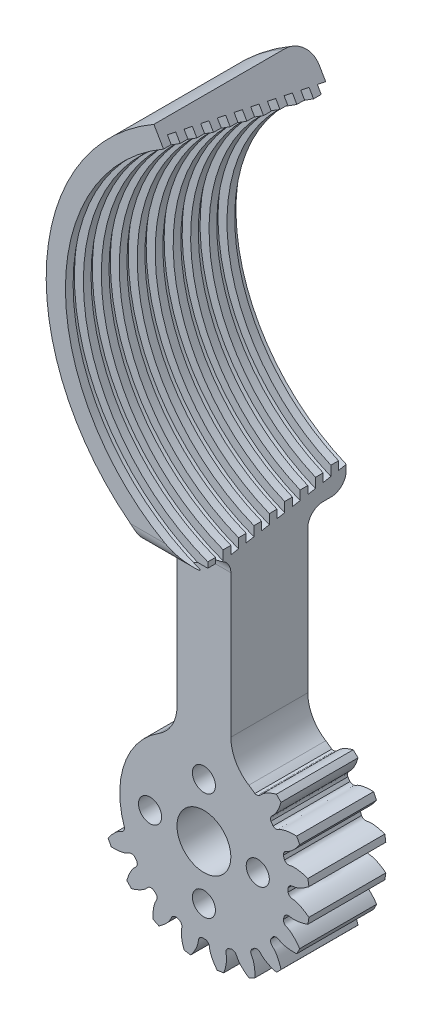
SolidWorks part; units mm, degrees
note: '?' marks a value the reader was unsure of.
material "聚脂树脂"
ref_plane "前视基准面" through (0, 0, 0) normal (0, 0, 1) x (1, 0, 0)
ref_plane "上视基准面" through (0, 0, 0) normal (0, 1, 0) x (1, 0, 0)
ref_plane "右视基准面" through (0, 0, 0) normal (1, 0, 0) x (0, 0, -1)
other "Configuration Table"
sketch "草图1" plane through (0, 0, 0) normal (0, 0, 1) x (1, 0, 0)
  circle A0 centre (0, 0) radius 13.75
extrude "凸台-拉伸1" add sketch "草图1" along normal blind 10
ref_axis "基准轴1" through (0, 0, -1.5) along (0, 0, 1)?
sketch "草图2" plane through (0, 0, 0) normal (0, 0, 1) x (1, 0, 0)
  line L0 (0, 0) -> (0, 13.75) construction
  circle A0 centre (0, 0) radius 13.75 construction
  arc A1 (0.2416, 10.9348) -> (-0.2416, 10.9348) centre (0, 0) ccw
  arc A2 (3.9764, 15.6228) -> (-3.9764, 15.6228) centre (0, 0) ccw
  spline S0 degree 3 poles (0.2416, 10.9348) (0.764, 11.1168) (0.6964, 11.4839) (0.7661, 11.8375) (0.7736, 11.8719) (0.7829, 11.9108) (0.7941, 11.954) (0.8075, 12.0015) (0.8231, 12.0532) (0.8413, 12.1091) (0.8621, 12.169) (0.8857, 12.2329) (0.9123, 12.3007) (0.9421, 12.3723) (0.9752, 12.4476) (1.0117, 12.5264) (1.0519, 12.6088) (1.0959, 12.6945) (1.1438, 12.7834) (1.1957, 12.8755) (1.2519, 12.9705) (1.3125, 13.0684) (1.3775, 13.1691) (1.4472, 13.2723) (1.5216, 13.3779) (1.601, 13.4858) (1.6853, 13.5958) (1.7747, 13.7078) (1.8694, 13.8216) (1.9693, 13.937) (2.0748, 14.0539) (2.1857, 14.1721) (2.3023, 14.2914) (2.4246, 14.4116) (2.5527, 14.5326) (2.6866, 14.6542) (2.8265, 14.7761) (2.9725, 14.8983) (3.1245, 15.0204) (3.2826, 15.1424) (3.4469, 15.2639) (3.6768, 15.427) (3.8549, 15.5454) (3.9764, 15.6228) knots 0 0 0 0 0.165916 0.170906 0.176664 0.183189 0.190482 0.198542 0.207371 0.216967 0.22733 0.238462 0.250361 0.263027 0.276462 0.290664 0.305634 0.321371 0.337876 0.355149 0.37319 0.391998 0.411574 0.431917 0.453028 0.474907 0.497554 0.520968 0.54515 0.570099 0.595817 0.622302 0.649554 0.677575 0.706363 0.735918 0.766242 0.797333 0.829191 0.861818 0.895212 0.929373 1 1 1 1
  spline S1 degree 3 poles (-0.2416, 10.9348) (-0.764, 11.1168) (-0.6964, 11.4839) (-0.7661, 11.8375) (-0.7736, 11.8719) (-0.7829, 11.9108) (-0.7941, 11.954) (-0.8075, 12.0015) (-0.8231, 12.0532) (-0.8413, 12.1091) (-0.8621, 12.169) (-0.8857, 12.2329) (-0.9123, 12.3007) (-0.9421, 12.3723) (-0.9752, 12.4476) (-1.0117, 12.5264) (-1.0519, 12.6088) (-1.0959, 12.6945) (-1.1438, 12.7834) (-1.1957, 12.8755) (-1.2519, 12.9705) (-1.3125, 13.0684) (-1.3775, 13.1691) (-1.4472, 13.2723) (-1.5216, 13.3779) (-1.601, 13.4858) (-1.6853, 13.5958) (-1.7747, 13.7078) (-1.8694, 13.8216) (-1.9693, 13.937) (-2.0748, 14.0539) (-2.1857, 14.1721) (-2.3023, 14.2914) (-2.4246, 14.4116) (-2.5527, 14.5326) (-2.6866, 14.6542) (-2.8265, 14.7761) (-2.9725, 14.8983) (-3.1245, 15.0204) (-3.2826, 15.1424) (-3.4469, 15.2639) (-3.6768, 15.427) (-3.8549, 15.5454) (-3.9764, 15.6228) knots 0 0 0 0 0.165916 0.170906 0.176664 0.183189 0.190482 0.198542 0.207371 0.216967 0.22733 0.238462 0.250361 0.263027 0.276462 0.290664 0.305634 0.321371 0.337876 0.355149 0.37319 0.391998 0.411574 0.431917 0.453028 0.474907 0.497554 0.520968 0.54515 0.570099 0.595817 0.622302 0.649554 0.677575 0.706363 0.735918 0.766242 0.797333 0.829191 0.861818 0.895212 0.929373 1 1 1 1
extrude "切除-拉伸1" cut sketch "草图2" along normal through all
pattern_circular "阵列(圆周)1" count 20 every 18 about axis through (0, 0, -1.5) along (0, 0, 1) of "切除-拉伸1"
sketch "草图6" plane through (0, 0, 0) normal (0, 0, -1) x (-1, 0, 0)
  line L0 (0, 0) -> (0, 65.9124) construction
  line L1 (0, 0) -> (39.45, 0) construction
  line L2 (0, 0) -> (-30.8379, 0) construction
  line L3 (-12.5, 0) -> (-12.5, 56.4778) construction
  line L4 (3.5, 0) -> (3.5, 35.9714)
  line L5 (-3.5, 0) -> (-3.5, 35.9714)
  line L6 (-3.5, 35.9714) -> (-3.5, 73.8085)
  line L7 (-3.5, 73.8085) -> (-12.5, 58.22) construction
  line L8 (-3.5, 73.8085) -> (6.3052, 90.7916) construction
  line L9 (-3.5, 73.8085) -> (1.2022, 81.9529)
  line L10 (-3.5, 0) -> (3.5, 0)
  line L11 (-5.8534, 12.4419) -> (-3.5, 13.8006)
  line L12 (5.8534, 12.4419) -> (3.5, 13.8006)
  line L13 (1.5, 82.4687) -> (1.2022, 81.9529)
  circle A0 centre (0, 0) radius 12.5 construction
  circle A1 centre (-12.5, 58.22) radius 24 construction
  circle A2 centre (-12.5, 58.22) radius 27.4044 construction
  arc A3 (1.2022, 81.9529) -> (3.5, 35.9714) centre (-12.5, 58.22) cw
  arc A4 (-0.5, 79.0046) -> (-3.5, 35.9714) centre (-12.5, 58.22) cw
  circle A5 centre (-12.5, 58.22) radius 28 construction
  arc A6 (1.5, 82.4687) -> (3.5, 35.2417) centre (-12.5, 58.22) cw
  spline S0 degree 3 poles (3336.5295, 2210.1081) (-34.3582, -18.9006) (-1.4548, 5.7671) (-4.3931, 11.033) (-4.4189, 11.076) (-4.4589, 11.1387) (-4.5098, 11.2131) (-4.5827, 11.3111) (-4.6712, 11.4208) (-4.7765, 11.541) (-4.8994, 11.6706) (-5.0408, 11.8083) (-5.2016, 11.9528) (-5.3825, 12.1027) (-5.5474, 12.2287) (-5.6899, 12.331) (-30.4612, 29.3782) (-162.3521, -112.6914) (3699.4893, 1518.05) knots -2.772458 -2.772458 -2.772458 -2.772458 0.165916 0.170906 0.183189 0.190482 0.207371 0.22733 0.250361 0.276462 0.305634 0.337876 0.37319 0.411574 0.453028 0.474907 0.497554 15.191814 15.191814 15.191814 15.191814 only from (-3.6089, 10.325) to (-5.8534, 12.4419) construction
  spline S1 degree 3 poles (-3.5, 10.3269) (-4.1564, 10.2919) (-4.2008, 10.6883) (-4.3931, 11.033) (-4.4189, 11.076) (-4.4589, 11.1387) (-4.5098, 11.2131) (-4.5827, 11.3111) (-4.6712, 11.4208) (-4.7765, 11.541) (-4.8994, 11.6706) (-5.0408, 11.8083) (-5.2016, 11.9528) (-5.3825, 12.1027) (-5.5842, 12.2567) (-5.7442, 12.3691) (-5.8366, 12.4308) (-5.8534, 12.4419) knots -0.010289 -0.010289 -0.010289 -0.010289 0.165916 0.170906 0.183189 0.190482 0.207371 0.22733 0.250361 0.276462 0.305634 0.337876 0.37319 0.411574 0.453028 0.497554 0.507432 0.507432 0.507432 0.507432
  spline S2 degree 3 poles (-3336.5295, 2210.1081) (34.3582, -18.9006) (1.4548, 5.7671) (4.3931, 11.033) (4.4189, 11.076) (4.4589, 11.1387) (4.5098, 11.2131) (4.5827, 11.3111) (4.6712, 11.4208) (4.7765, 11.541) (4.8994, 11.6706) (5.0408, 11.8083) (5.2016, 11.9528) (5.3825, 12.1027) (5.5474, 12.2287) (5.6899, 12.331) (30.4612, 29.3782) (162.3521, -112.6914) (-3699.4893, 1518.05) knots -2.27989 -2.27989 -2.27989 -2.27989 0.658484 0.663474 0.675757 0.68305 0.699939 0.719899 0.742929 0.76903 0.798202 0.830445 0.865758 0.904142 0.945597 0.967475 0.990122 15.684382 15.684382 15.684382 15.684382 only from (3.6089, 10.325) to (5.8534, 12.4419) construction
  spline S3 degree 3 poles (3.5, 10.3269) (4.1564, 10.2919) (4.2008, 10.6883) (4.3931, 11.033) (4.4189, 11.076) (4.4589, 11.1387) (4.5098, 11.2131) (4.5827, 11.3111) (4.6712, 11.4208) (4.7765, 11.541) (4.8994, 11.6706) (5.0408, 11.8083) (5.2016, 11.9528) (5.3825, 12.1027) (5.5842, 12.2567) (5.7442, 12.3691) (5.8366, 12.4308) (5.8534, 12.4419) knots 0.482279 0.482279 0.482279 0.482279 0.658484 0.663474 0.675757 0.68305 0.699939 0.719899 0.742929 0.76903 0.798202 0.830445 0.865758 0.904142 0.945597 0.990122 1 1 1 1
  dimension "D1" = 25
  dimension "D4" = 48
  dimension "D5" = 30
  dimension "D8" = 56
  dimension "D2" = 7
  dimension "D3" = 58.22
  dimension "D6" = 60
  dimension "D7" = 60
extrude "凸台-拉伸2" add sketch "草图6" against normal blind 15 and the other way blind 5 contours A3 L9 L6 L5 L10 L4 | S1 L5 L11 | L4 S3 L12 | A4 L9 L6 | A6 L13 A3 L4
sketch "草图7" plane through (3.5, 0, 0) normal (1, 0, 0) x (0, 0, -1)
  line L0 (0, 0) -> (0, 34)
  line L1 (0, 34) -> (5, 34)
  line L3 (5, 34) -> (5, 0)
  line L4 (5, 0) -> (0, 0) construction
  line L5 (5, 0) -> (5, 10.3269) construction
  line L6 (5, 0) -> (0, 0)
  line L7 (-5, 2.5777) -> (-5, 27.3083) construction
  line L8 (-10, 2.5777) -> (0, 2.5777) construction
  line L9 (-15, 34) -> (-15, 0)
  line L10 (-10, 34) -> (-15, 34)
  line L11 (-10, 0) -> (-10, 34)
  line L12 (-15, 0) -> (-10, 0)
  dimension "D1" = 34
extrude "切除-拉伸3" cut sketch "草图7" against normal blind 32 and the other way blind 10
ref_plane "基准面1" through (12.5, 0, 0) normal (1, 0, 0) x (0, 0, -1)
fillet "圆角2" radius 2 4 edges at (0, 34, 10) (0, 34, 15) (0, 34, 0) (0, 34, -5)
sketch "草图4" plane through (0, 0, 10) normal (0, 0, 1) x (1, 0, 0)
  line L0 (0, 0) -> (0, 14.4175) construction
  line L1 (0, 0) -> (19.7904, 0) construction
  circle A0 centre (0, 0) radius 9
  circle A1 centre (0, 0) radius 3.5
  circle A2 centre (0, 7) radius 1.5
  circle A3 centre (7, 0) radius 1.5
  circle A4 centre (0, -7) radius 1.5
  circle A5 centre (-7, 0) radius 1.5
  dimension "D1" = 18
  dimension "D2" = 7
  dimension "D3" = 3
  dimension "D4" = 3
  dimension "D5" = 7
  dimension "D6" = 7
extrude "切除-拉伸2" cut sketch "草图4" against normal blind 20 contours A1 | A5 | A2 | A3 | A4
ref_plane "基准面2" through (0, 0, 9) normal (0, 0, 1) x (1, 0, 0)
sketch "草图17" plane through (0, 0, 10) normal (0, 0, 1) x (1, 0, 0)
  line L0 (0, 0) -> (-6.6228, 8.7044)
  line L1 (-6.6228, 8.7044) -> (-11.857, 15.5837)
  line L2 (0, 0) -> (-10.325, -3.6089)
  line L3 (-10.325, -3.6089) -> (-17.9409, -6.2709)
  circle A0 centre (0, 0) radius 10.9375
  arc A1 (-6.2318, 8.9885) -> (-6.6228, 8.7044) centre (0, 0) ccw construction
  circle A2 centre (0, 0) radius 17.5
  dimension "D1" = 35
extrude "切除-拉伸5" cut sketch "草图17" against normal blind 10 contours L1 A2 L3 A0
sketch "草图20" plane through (0, 0, 0) normal (0, 0, -1) x (-1, 0, 0)
  line L0 (-3.5, 13.8006) -> (-3.5, 10.3624)
  line L1 (3.5, 13.8006) -> (3.5, 10.3624)
  line L2 (5.8534, 12.4419) -> (3.5, 13.8006) construction
  line L3 (-5.8534, 12.4419) -> (-3.5, 13.8006) construction
  line L4 (5.8534, 12.4419) -> (3.5, 13.8006)
  line L5 (-5.8534, 12.4419) -> (-3.5, 13.8006)
  circle A0 centre (0, 0) radius 10.9375
  arc A1 (10.325, -3.6089) -> (6.2318, 8.9885) centre (0, 0) ccw construction
  arc A2 (6.6252, 12.0486) -> (5.8534, 12.4419) centre (0, 0) ccw construction
  arc A3 (-5.8534, 12.4419) -> (-6.6252, 12.0486) centre (0, 0) ccw construction
  arc A4 (6.6252, 12.0486) -> (5.8534, 12.4419) centre (0, 0) ccw
  arc A5 (-5.8534, 12.4419) -> (-6.6252, 12.0486) centre (0, 0) ccw
  spline S0 degree 3 poles (940.4852, -347.6041) (-11.6727, 10.1742) (4.7326, 6.5586) (6.3437, 10.0391) (6.3633, 10.0853) (6.3905, 10.1545) (6.4208, 10.2394) (6.4573, 10.356) (6.4939, 10.4921) (6.5293, 10.6479) (6.5619, 10.8235) (6.5902, 11.0188) (6.6126, 11.2338) (6.6276, 11.4683) (6.6325, 11.6758) (6.6315, 11.8512) (6.1325, 31.3668) (-75.0291, 47.9678) (845.3646, -532.4841) knots -1.696649 -1.696649 -1.696649 -1.696649 0.165916 0.170906 0.183189 0.190482 0.207371 0.22733 0.250361 0.276462 0.305634 0.337876 0.37319 0.411574 0.453028 0.474907 0.497554 10.021595 10.021595 10.021595 10.021595 only from (6.2318, 8.9885) to (6.6252, 12.0486) construction
  spline S1 degree 3 poles (-940.4852, -347.6041) (11.6727, 10.1742) (-4.7326, 6.5586) (-6.3437, 10.0391) (-6.3633, 10.0853) (-6.3905, 10.1545) (-6.4208, 10.2394) (-6.4573, 10.356) (-6.4939, 10.4921) (-6.5293, 10.6479) (-6.5619, 10.8235) (-6.5902, 11.0188) (-6.6126, 11.2338) (-6.6276, 11.4683) (-6.6325, 11.6758) (-6.6315, 11.8512) (-6.1325, 31.3668) (75.0291, 47.9678) (-845.3646, -532.4841) knots -1.204081 -1.204081 -1.204081 -1.204081 0.658484 0.663474 0.675757 0.68305 0.699939 0.719899 0.742929 0.76903 0.798202 0.830445 0.865758 0.904142 0.945597 0.967475 0.990122 10.514164 10.514164 10.514164 10.514164 only from (-6.2318, 8.9885) to (-6.6252, 12.0486) construction
  spline S2 degree 3 poles (6.2318, 8.9885) (5.9162, 9.4428) (6.1867, 9.7) (6.3437, 10.0391) (6.3633, 10.0853) (6.3905, 10.1545) (6.4208, 10.2394) (6.4573, 10.356) (6.4939, 10.4921) (6.5293, 10.6479) (6.5619, 10.8235) (6.5902, 11.0188) (6.6126, 11.2338) (6.6276, 11.4683) (6.6336, 11.722) (6.6305, 11.9176) (6.6261, 12.0285) (6.6252, 12.0486) knots 0 0 0 0 0.165916 0.170906 0.183189 0.190482 0.207371 0.22733 0.250361 0.276462 0.305634 0.337876 0.37319 0.411574 0.453028 0.497554 0.507432 0.507432 0.507432 0.507432
  spline S3 degree 3 poles (-6.2318, 8.9885) (-5.9162, 9.4428) (-6.1867, 9.7) (-6.3437, 10.0391) (-6.3633, 10.0853) (-6.3905, 10.1545) (-6.4208, 10.2394) (-6.4573, 10.356) (-6.4939, 10.4921) (-6.5293, 10.6479) (-6.5619, 10.8235) (-6.5902, 11.0188) (-6.6126, 11.2338) (-6.6276, 11.4683) (-6.6336, 11.722) (-6.6305, 11.9176) (-6.6261, 12.0285) (-6.6252, 12.0486) knots 0.492568 0.492568 0.492568 0.492568 0.658484 0.663474 0.675757 0.68305 0.699939 0.719899 0.742929 0.76903 0.798202 0.830445 0.865758 0.904142 0.945597 0.990122 1 1 1 1
extrude "切除-拉伸7" cut sketch "草图20" against normal blind 10 contours S3 A0 L0 L5 A5 | A0 S2 A4 L4 L1
fillet "圆角7" radius 5 2 edges at (3.5, 10.3624, 5) (-3.5, 10.3624, 5)
ref_plane "基准面4" through (0, 58.22, 0) normal (0, 1, 0) x (1, 0, 0)
ref_axis "基准轴3" through (12.5, 58.22, -6) along (0, 0, 1)?
sketch "草图21" plane through (12.5, 0, 0) normal (1, 0, 0) x (0, 0, -1)
  line L0 (0, 0) -> (12.6235, 0) construction
  line L1 (-41.0199, 58.22) -> (51.9091, 58.22) construction
  line L6 (-5, 13.4816) -> (-5, 87.3784) construction
  line L7 (-10, 13.4816) -> (0, 13.4816) construction
  line L12 (-35, 58.22) -> (-35, 88.22)
  line L13 (-35, 88.22) -> (25, 78.22)
  line L14 (25, 78.22) -> (25, 58.22)
  line L15 (25, 58.22) -> (-35, 58.22)
  line L16 (-15, 82.4687) -> (-15, 87.908) construction
  line L17 (5, 73.8085) -> (5, 87.908) construction
  line L18 (-15, 84.8867) -> (-15, 83.72)
  line L19 (-15, 83.72) -> (-14, 83.72)
  line L20 (-14, 83.72) -> (-14, 84.72)
  line L21 (-13, 84.5533) -> (-13, 83.3867)
  line L22 (-13, 83.3867) -> (-12, 83.3867)
  line L23 (-12, 83.3867) -> (-12, 84.3867)
  line L24 (-11, 84.22) -> (-11, 83.0533)
  line L25 (-11, 83.0533) -> (-10, 83.0533)
  line L26 (-10, 83.0533) -> (-10, 84.0533)
  line L27 (-9, 83.8867) -> (-9, 82.72)
  line L28 (-9, 82.72) -> (-8, 82.72)
  line L29 (-8, 82.72) -> (-8, 83.72)
  line L30 (-7, 83.5533) -> (-7, 82.3867)
  line L31 (-7, 82.3867) -> (-6, 82.3867)
  line L32 (-6, 82.3867) -> (-6, 83.3867)
  line L33 (-5, 83.22) -> (-5, 82.0533)
  line L34 (-5, 82.0533) -> (-4, 82.0533)
  line L35 (-4, 82.0533) -> (-4, 83.0533)
  line L36 (-3, 82.8867) -> (-3, 81.72)
  line L37 (-3, 81.72) -> (-2, 81.72)
  line L38 (-2, 81.72) -> (-2, 82.72)
  line L39 (-1, 82.5533) -> (-1, 81.4472)
  line L40 (-1, 81.4472) -> (0, 81.4472)
  line L41 (0, 81.4472) -> (0, 82.3867)
  line L42 (1, 82.22) -> (1, 81.0533)
  line L43 (1, 81.0533) -> (2, 81.0533)
  line L44 (2, 81.0533) -> (2, 82.0533)
  line L45 (3, 81.8867) -> (3, 80.72)
  line L46 (3, 80.72) -> (4, 80.72)
  line L47 (4, 80.72) -> (4, 81.72)
  dimension "D1" = 58.22
  dimension "D2" = 30
  dimension "D3" = 20
  dimension "D4" = 60
  dimension "D5" = 30
  dimension "D6" = 1
  dimension "D7" = 1
  dimension "D8" = 1
  dimension "D9" = 1
  dimension "D10" = 1
  dimension "D11" = 1
  dimension "D12" = 1
  dimension "D13" = 1
  dimension "D14" = 1
  dimension "D15" = 1
  dimension "D16" = 1
  dimension "D17" = 1
  dimension "D18" = 1
  dimension "D19" = 1
  dimension "D20" = 1
  dimension "D21" = 1
  dimension "D22" = 1
  dimension "D24" = 1
  dimension "D25" = 1
  dimension "D26" = 1
  dimension "D27" = 1
  dimension "D28" = 1
  dimension "D29" = 1
  dimension "D30" = 1
  dimension "D31" = 0.9394
  dimension "D32" = 1
  dimension "D33" = 1
  dimension "D34" = 1
  dimension "D35" = 1
revolve "切除-旋转7" cut sketch "草图21" angle 360 about L1
fillet "圆角8" radius 3 1 edges at (-15.4404, 60.0463, -5)
fillet "圆角9" radius 3 2 edges at (-3.5, 35.821, -3.6175) (-3.5, 35.2417, 6.4253)
